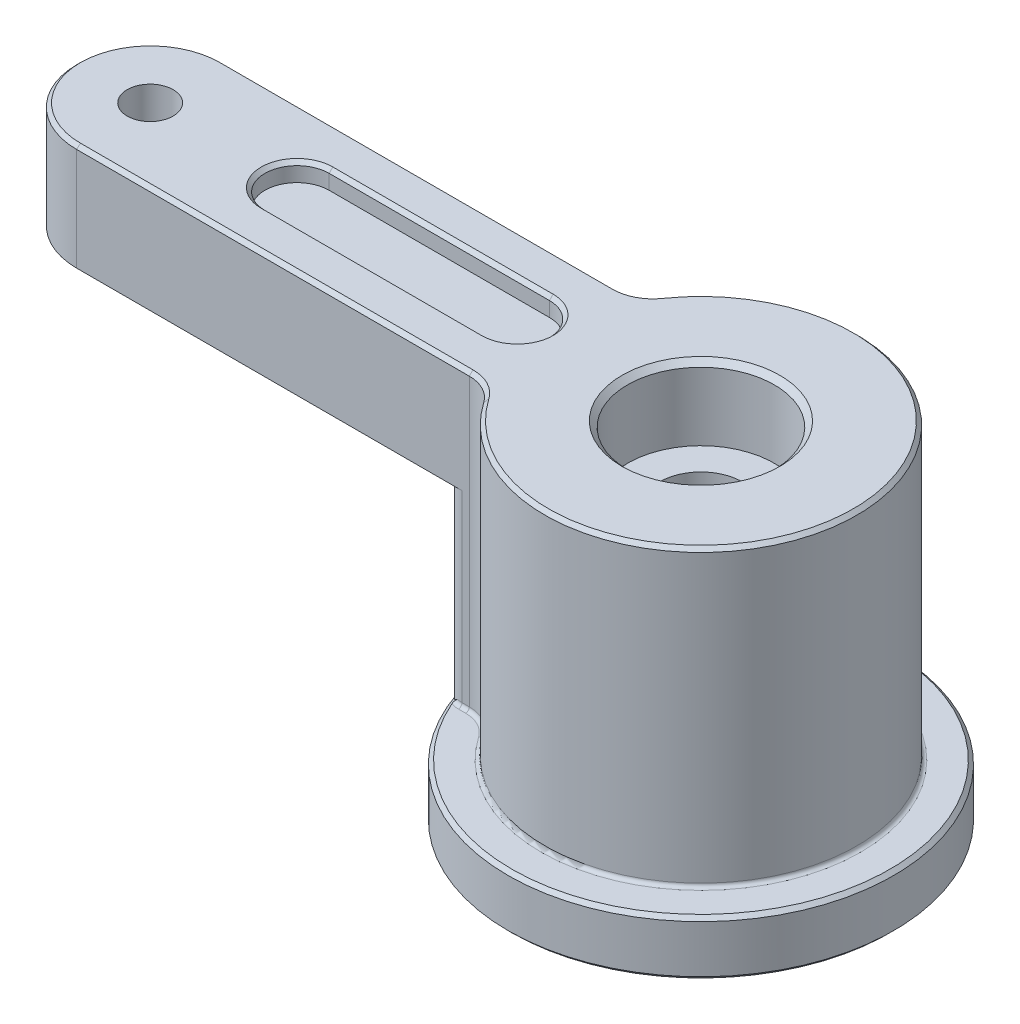
SolidWorks part; units mm, degrees
material "A5052"
ref_plane "Front Plane" through (0, 0, 0) normal (0, 0, 1) x (1, 0, 0)
ref_plane "Top Plane" through (0, 0, 0) normal (0, 1, 0) x (1, 0, 0)
ref_plane "Right Plane" through (0, 0, 0) normal (1, 0, 0) x (0, 0, -1)
sketch "Sketch1" plane through (0, 0, 0) normal (0, 1, 0) x (1, 0, 0)
  circle A0 centre (0, 0) radius 8.5
  dimension "D1" = 17
extrude "Boss-Extrude1" add sketch "Sketch1" along normal blind 15
sketch "Sketch2" plane through (0, 15, 0) normal (0, 1, 0) x (1, 0, 0)
  circle A0 centre (0, 0) radius 8.5
  dimension "D1" = 17
extrude "Boss-Extrude2" add sketch "Sketch2" against normal blind 10
sketch "Sketch3" plane through (0, 15, 0) normal (0, 1, 0) x (1, 0, 0)
  line L0 (0, 0) -> (-30, 0) construction
  line L1 (0, -4) -> (-30, -4)
  line L2 (0, 4) -> (-30, 4)
  arc A0 (0, -4) -> (0, 4) centre (0, 0) ccw
  arc A1 (-30, 4) -> (-30, -4) centre (-30, 0) ccw
  point P3 (-15, 0)
  dimension "D1" = 8
  dimension "D2" = 30
extrude "Boss-Extrude3" add sketch "Sketch3" against normal blind 6
fillet "Fillet8" radius 2 2 edges at (-7.5, 12, -4) (-7.5, 12, 4)
hole_wizard "CBORE for M4 SHCS1" positions "Sketch5" profile "Sketch6" counterbore size "M4" standard "ANSI Metric" end condition through all
sketch "Sketch5" plane through (0, 15, 0) normal (0, 1, 0) x (1, 0, 0)
  point P0 (0, 0)
sketch "Sketch6" plane through (0, 15, 0) normal (1, 0, 0) x (0, 0, 1)
  line L0 (0, 0) -> (0, 15)
  line L1 (0, 15) -> (2.25, 15)
  line L3 (2.25, 15) -> (2.25, 4)
  line L4 (2.25, 4) -> (4, 4)
  line L5 (4, 4) -> (4, 0)
  line L7 (4, 0) -> (0, 0)
  line L11 (0, -6.35) -> (0, 107.95) construction
  dimension "Thru Hole Dia." = 4.5
  dimension "Thru Hole Depth" = 15
  dimension "C'Bore Dia." = 8
  dimension "C'Bore Depth" = 4
chamfer "Chamfer4" distance 0.3 angle 45 1 edges at (0, 15, 4)
sketch "Sketch16" plane through (0, 0, 0) normal (0, -1, 0) x (1, 0, 0)
  circle A0 centre (0, 0) radius 8.5 construction
  circle A1 centre (0, 0) radius 8.5
  circle A2 centre (0, 0) radius 2.25
  circle A3 centre (0, 0) radius 2.25 construction
extrude "Boss-Extrude4" add sketch "Sketch16" along normal blind 4
sketch "Sketch17" plane through (0, 0, 0) normal (0, 0, 1) x (1, 0, 0)
  line L0 (0, 0) -> (0, -5.5086) construction
  line L1 (8.5, -4) -> (10.5, -4)
  line L2 (8.5, -4) -> (8.5, -1)
  line L3 (8.5, -1) -> (10.5, -1)
  line L4 (10.5, -4) -> (10.5, -1)
  dimension "D1" = 3
  dimension "D2" = 2
revolve "Revolve1" add sketch "Sketch17" angle 360 about L0
sketch "Sketch21" plane through (0, 9, 0) normal (0, -1, 0) x (1, 0, 0)
  line L2 (-30, -4) -> (-8.6168, -4)
  line L3 (-8.6168, 4) -> (-30, 4)
  line L4 (-9.7082, -4) -> (-8.6168, -4)
  line L5 (-8.6168, 4) -> (-9.7082, 4)
  circle A0 centre (0, 0) radius 10.5 construction
  arc A1 (-9.7082, 4) -> (-9.7082, -4) centre (0, 0) ccw
  arc A4 (-6.9755, -4.8571) -> (-8.6168, -4) centre (-8.6168, -6) ccw
  arc A5 (-6.9755, 4.8571) -> (-6.9755, -4.8571) centre (0, 0) ccw
  arc A6 (-8.6168, 4) -> (-6.9755, 4.8571) centre (-8.6168, 6) ccw
  arc A7 (-30, 4) -> (-30, -4) centre (-30, 0) ccw
  arc A8 (-6.9755, -4.8571) -> (-8.6168, -4) centre (-8.6168, -6) ccw
  arc A9 (-6.9755, 4.8571) -> (-6.9755, -4.8571) centre (0, 0) ccw
  arc A10 (-8.6168, 4) -> (-6.9755, 4.8571) centre (-8.6168, 6) ccw
  dimension "D1" = 0
extrude "Boss-Extrude5" add sketch "Sketch21" along normal up to surface (10 mm away) up to face at (0, -1, -8.5)
fillet "Fillet9" radius 1 2 edges at (-9.7082, 4, -4) (-9.7082, 4, 4)
chamfer "Chamfer7" distance 0.2 angle 45 6 edges at (-7.691, 15, -4.2272) (-19.3084, 15, -4) (8.5, 15, 0) (-34, 15, 0) (-7.691, 15, 4.2272) (-19.3084, 15, 4)
chamfer "Chamfer8" distance 0.2 angle 45 3 edges at (-19.5069, 9, -4) (-34, 9, 0) (-19.5069, 9, 4)
hole_wizard "M3x0.5 Tapped Hole1" positions "Sketch23" profile "Sketch24" tap size "M3x0.5" standard "ANSI Metric" end condition through all
sketch "Sketch23" plane through (0, 15, 0) normal (0, 1, 0) x (1, 0, 0)
  point P0 (-30, 0)
sketch "Sketch24" plane through (-30, 15, 0) normal (1, 0, 0) x (0, 0, 1)
  line L0 (0, 0) -> (0, 19)
  line L1 (0, 19) -> (1.25, 19)
  line L2 (1.25, 19) -> (1.25, 0)
  line L5 (1.25, 0) -> (0, 0)
  line L11 (0, -6.35) -> (0, 107.95) construction
  dimension "Thru Tap Drill Dia." = 2.5
  dimension "Thru Tap Drill Depth" = 19
cosmetic thread "Hole Thread1" parameters "D2"=3
sketch "Sketch25" plane through (0, 15, 0) normal (0, 1, 0) x (1, 0, 0)
  line L0 (-22, 0) -> (-10, 0) construction
  line L1 (-22, 1.75) -> (-10, 1.75)
  line L2 (-22, -1.75) -> (-10, -1.75)
  arc A0 (-22, 1.75) -> (-22, -1.75) centre (-22, 0) ccw
  arc A1 (-10, -1.75) -> (-10, 1.75) centre (-10, 0) ccw
  circle A2 centre (-30, 0) radius 1.25 construction
  point P3 (-16, 0)
  dimension "D2" = 8
  dimension "D1" = 3.5
  dimension "D3" = 10
extrude "Cut-Extrude9" cut sketch "Sketch25" against normal blind 1
chamfer "Chamfer10" distance 0.2 angle 45 4 edges at (-16, 15, 1.75) (-8.25, 15, 0) (-23.75, 15, 0) (-16, 15, -1.75)
sketch "Sketch28" plane through (0, -4, 0) normal (0, -1, 0) x (1, 0, 0)
  circle A0 centre (0, 0) radius 4.75
  circle A1 centre (0, 0) radius 2.25 construction
  circle A2 centre (0, 0) radius 2.25
  dimension "D1" = 9.5
extrude "Boss-Extrude6" add sketch "Sketch28" along normal blind 1
sketch "Sketch27" plane through (0, -5, 0) normal (0, -1, 0) x (1, 0, 0)
  line L1 (-3.05, 3.05) -> (3.05, 3.05)
  line L2 (-3.05, 3.05) -> (-3.05, -3.05)
  line L3 (-3.05, -3.05) -> (3.05, -3.05)
  line L4 (3.05, 3.05) -> (3.05, -3.05)
  line L5 (-3.05, 3.05) -> (3.05, -3.05) construction
  line L6 (-3.05, -3.05) -> (3.05, 3.05) construction
  point P0 (0, 0)
  dimension "D1" = 6.1
  dimension "D2" = 6.1
extrude "Cut-Extrude10" cut sketch "Sketch27" against normal blind 3
fillet "Fillet12" radius 1.5 4 edges at (-3.05, -3.5, -3.05) (-3.05, -3.5, 3.05) (3.05, -3.5, 3.05) (3.05, -3.5, -3.05)
sketch "Sketch29" plane through (0, -5, 0) normal (0, -1, 0) x (1, 0, 0)
  circle A0 centre (0, 0) radius 4.05
  dimension "D1" = 8.1
extrude "Cut-Extrude11" [suppressed] cut sketch "Sketch29" against normal blind 1
sketch "Sketch30" plane through (0, -4, 0) normal (0, -1, 0) x (1, 0, 0)
  circle A0 centre (-8.5, 0) radius 1
  dimension "D1" = 2
extrude "Cut-Extrude12" cut sketch "Sketch30" against normal blind 3
chamfer "Chamfer11" distance 0.2 angle 45 2 edges at (10.5, -1, 0) (0, -4, 10.5)
fillet "Fillet13" radius 0.2 7 edges at (-9.2975, -1, -3.9589) (-8.8154, -1, -4) (-7.691, -1, -4.2272) (-9.2975, -1, 3.9589) (-8.8154, -1, 4) (-7.691, -1, 4.2272) (8.5, -1, 0)
